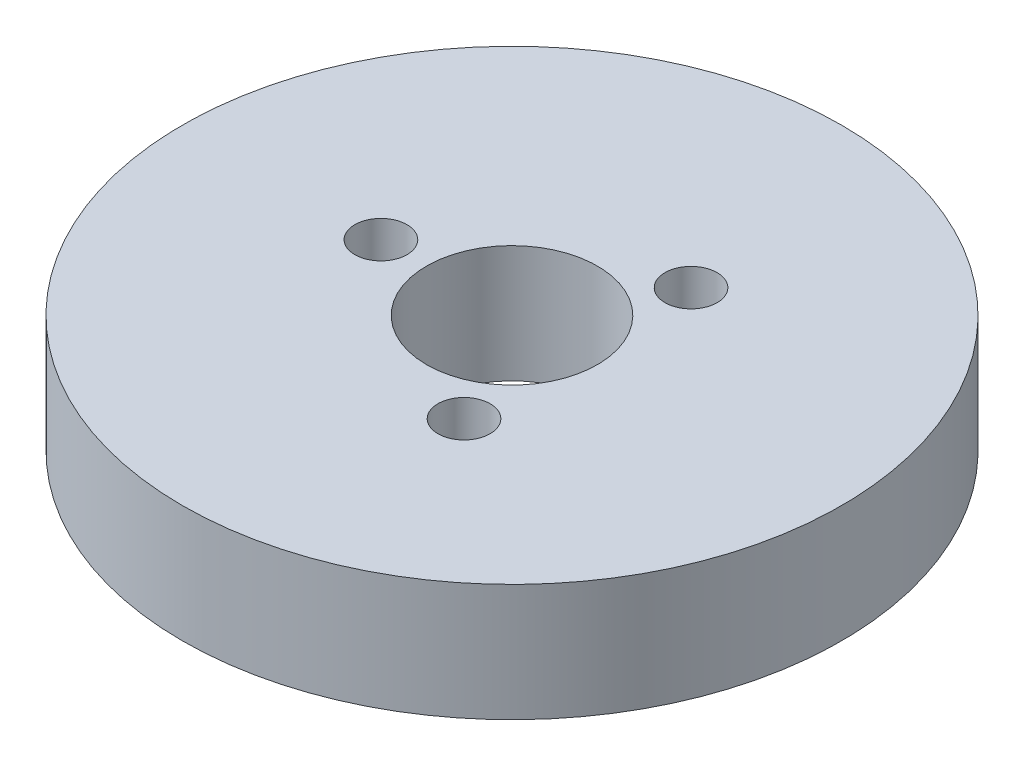
SolidWorks part; units mm, degrees
ref_plane "Front Plane" through (0, 0, 0) normal (0, 0, 1) x (1, 0, 0)
ref_plane "Top Plane" through (0, 0, 0) normal (0, 1, 0) x (1, 0, 0)
ref_plane "Right Plane" through (0, 0, 0) normal (1, 0, 0) x (0, 0, -1)
sketch "Sketch1" plane through (0, 0, 0) normal (0, 1, 0) x (1, 0, 0)
  circle A0 centre (0, 0) radius 67.5
  dimension "FLANGE_OD" = 135
extrude "Boss-Extrude1" add sketch "Sketch1" along normal blind 24
sketch "Sketch2" plane through (0, 0, 0) normal (0, 1, 0) x (1, 0, 0)
  circle A0 centre (0, 0) radius 17.5
  dimension "BORE_D" = 35
extrude "Cut-Extrude1" cut sketch "Sketch2" along normal through all
sketch "Sketch3" plane through (0, 24, 0) normal (0, 1, 0) x (1, 0, 0)
  circle A0 centre (0, 0) radius 26.8467 construction
  circle A1 centre (-26.8467, 0) radius 5.3388
  dimension "BOLT_D" = 10.6777
  dimension "BOLT_PCD" = 53.6934
extrude "Cut-Extrude2" cut sketch "Sketch3" against normal blind 15.7472
pattern_circular "CirPattern1" count 3 over 360 about axis through (0, 0, 0) along (0, 1, 0) of "Cut-Extrude2"
